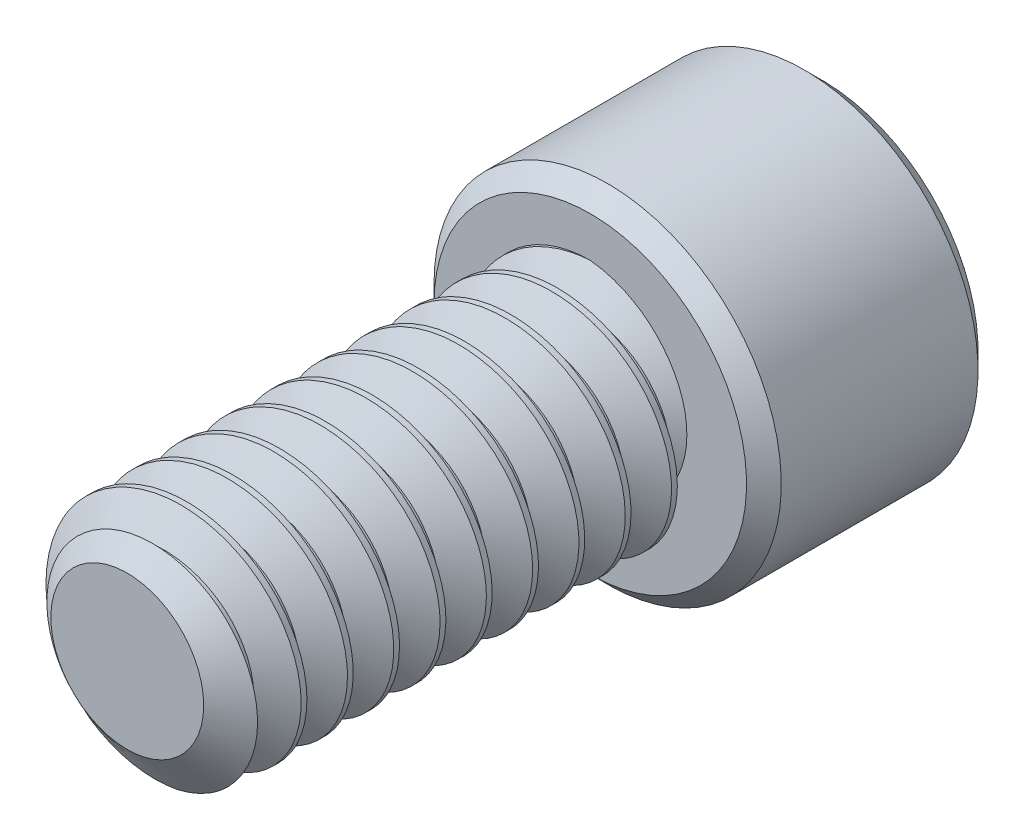
SolidWorks part; units mm, degrees
ref_plane "Front Plane" through (0, 0, 0) normal (0, 0, 1) x (1, 0, 0)
ref_plane "Top Plane" through (0, 0, 0) normal (0, 1, 0) x (1, 0, 0)
ref_plane "Right Plane" through (0, 0, 0) normal (1, 0, 0) x (0, 0, -1)
sketch "Sketch1" plane through (0, 0, 0) normal (0, 0, 1) x (1, 0, 0)
  circle A0 centre (0, 0) radius 3.175
  dimension "OD" = 6.35
extrude "Extrude1" add sketch "Sketch1" against normal blind 12.7
sketch "Sketch2" plane through (0, 0, 0) normal (0, 0, 1) x (1, 0, 0)
  circle A0 centre (0, 0) radius 3.175 construction
  circle A1 centre (0, 0) radius 3.175
curve "Helix/Spiral1" pitch 1.27 height 13.97 turns 11 parameters "pitch"=1.27
sketch "Sketch3" plane through (0, 0, 0) normal (1, 0, 0) x (0, 0, -1)
  line L0 (-1.1113, 3.175) -> (-0.635, 2.3501)
  line L1 (-0.635, 2.3501) -> (-0.4763, 2.3501)
  line L2 (-0.4763, 2.3501) -> (0, 3.175)
  line L3 (-1.1113, 3.175) -> (0, 3.175)
  line L4 (-0.5556, 3.175) -> (-0.5556, 2.3501) construction
  line L5 (-0.8731, 2.7626) -> (-0.2381, 2.7626) construction
  line L6 (0, 3.175) -> (0, -3.175) construction
  dimension "D1" = 0.1588
  dimension "D2" = 0.635
  dimension "D3" = 60
sweep "Cut-Sweep1" cut profiles "Sketch3" path "Helix/Spiral1"
sketch "Sketch4" plane through (0, 0, 0) normal (1, 0, 0) x (0, 0, -1)
  line L0 (0.7554, 3.175) -> (0, 2.0961)
  line L1 (0, 2.0961) -> (0, 3.175)
  line L2 (0.7554, 3.175) -> (0, 3.175)
  line L3 (-1.1113, 3.175) -> (0, 3.175) construction
  line L4 (0, 0) -> (7.0209, 0) construction
  dimension "D1" = 55
  dimension "D2" = 0.254
revolve "Cut-Revolve1" cut sketch "Sketch4" angle 360 about L4
sketch "Sketch5" plane through (0, 0, 0) normal (1, 0, 0) x (0, 0, -1)
  line L0 (12.7, -2.3728) -> (12.7, 2.2654) construction
  line L1 (12.7, 3.302) -> (87.4665, 3.302)
  line L2 (12.7, 3.302) -> (12.7, 0)
  line L3 (12.7, 0) -> (87.3125, 0)
  line L4 (87.3125, 2.9718) -> (87.3125, 0)
  line L5 (87.4665, 3.302) -> (87.3125, 2.9718)
  line L6 (0, 0) -> (9.9695, 0) construction
  point P3 (87.3125, 3.302)
  point P10 (87.3125, 3.302)
  dimension "D1" = 0.3302
  dimension "Thread min" = 87.3125
  dimension "D2" = 0.127
  dimension "D3" = 25
revolve "partially thread" add sketch "Sketch5" angle 360 about L6
sketch "Sketch6" plane through (0, 0, -12.7) normal (0, 0, -1) x (-1, 0, 0)
  circle A0 centre (0, 0) radius 4.7625
  dimension "head dia" = 9.525
extrude "Extrude2" add sketch "Sketch6" along normal blind 6.35
sketch "Sketch7" plane through (0, 0, -19.05) normal (0, 0, -1) x (-1, 0, 0)
  line L1 (0, 2.7496) -> (-2.3813, 1.3748)
  line L2 (-2.3813, 1.3748) -> (-2.3813, -1.3748)
  line L3 (-2.3813, -1.3748) -> (0, -2.7496)
  line L4 (0, -2.7496) -> (2.3813, -1.3748)
  line L5 (2.3813, -1.3748) -> (2.3813, 1.3748)
  line L6 (2.3813, 1.3748) -> (0, 2.7496)
  circle A0 centre (0, 0) radius 2.3813 construction
  dimension "hex dia" = 4.7625
extrude "Cut-Extrude1" cut sketch "Sketch7" against normal blind 3.5719
sketch "Sketch8" plane through (0, 0, -19.05) normal (0, 0, -1) x (-1, 0, 0)
  circle A0 centre (0, 0) radius 2.7496
extrude "Cut-Extrude2" cut sketch "Sketch8" against normal through all draft 45
chamfer "Chamfer1" distance 0.4763 angle 45 2 edges at (-4.7625, 0, -19.05) (-4.7625, 0, -12.7)
sketch "Sketch9" plane through (0, 0, 0) normal (1, 0, 0) x (0, 0, -1)
  line L0 (0, 3.175) -> (0, -3.175) construction
  line L1 (6.985, 3.175) -> (6.985, -3.175) construction
  dimension "D1" = 6.985
  dimension "D4" = 0.635
  dimension "D5" = 0.3302
equation "\"D3@Helix/Spiral1\" = \"screw length@Extrude1\"+\"pitch@Helix/Spiral1\""
equation "\"D1@Sketch3\" = \"pitch@Helix/Spiral1\"*.125"
equation "\"D2@Sketch3\" = \"pitch@Helix/Spiral1\"*.5"
equation "\"D1@Cut-Extrude1\" = \"hex dia@Sketch7\"*.75"
equation "\"D1@Chamfer1\" = \"head dia@Sketch6\"*.05"
equation "\"D1@Sketch9\" = \"pitch@Helix/Spiral1\"*5.5"
